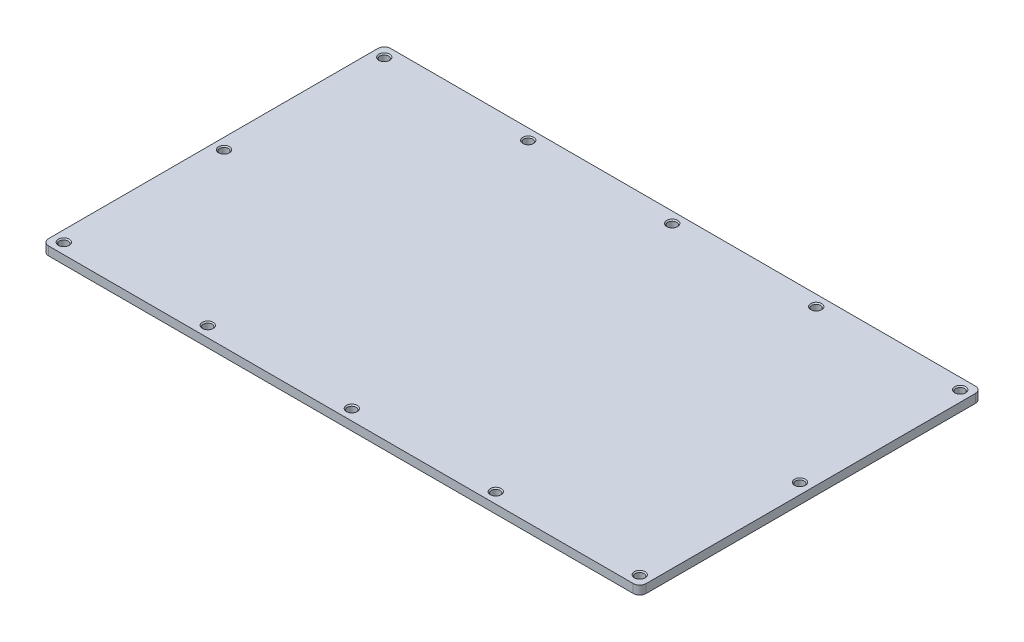
SolidWorks part; units mm, degrees
ref_plane "Front Plane" through (0, 0, 0) normal (0, 0, 1) x (1, 0, 0)
ref_plane "Top Plane" through (0, 0, 0) normal (0, 1, 0) x (1, 0, 0)
ref_plane "Right Plane" through (0, 0, 0) normal (1, 0, 0) x (0, 0, -1)
sketch "Sketch1" plane through (0, 0, 0) normal (0, 1, 0) x (1, 0, 0)
  line L0 (0, 0) -> (0, 158)
  line L1 (0, 158) -> (276, 158)
  line L2 (276, 158) -> (276, 0)
  line L3 (276, 0) -> (0, 0)
  dimension "D1" = 276
  dimension "D2" = 158
extrude "Boss-Extrude1" add sketch "Sketch1" along normal blind 4
sketch "Sketch2" plane through (0, 0, 0) normal (0, 1, 0) x (1, 0, 0)
  line L0 (5, 158) -> (5, 0) construction
  line L1 (276, 158) -> (0, 158) construction
  line L2 (0, 0) -> (276, 0) construction
  line L3 (0, 158) -> (0, 0) construction
  circle A0 centre (5, 79) radius 2
  dimension "D2" = 4
  dimension "D1" = 5
extrude "Cut-Extrude1" cut sketch "Sketch2" along normal blind 10
pattern_linear "LPattern1" count 2 spacing 74 along (0, 0, 1) count 2 spacing 74 along (0, 0, -1) of "Cut-Extrude1"
pattern_linear "LPattern2" count 5 spacing 66.5 along (1, 0, 0) of "LPattern1", "Cut-Extrude1"
fillet "Fillet1" radius 3 4 edges at (276, 2, 0) (276, 2, -158) (0, 2, -158) (0, 2, 0)
sketch "Sketch3" plane through (0, 0, 0) normal (0, 1, 0) x (1, 0, 0)
  line L0 (30.6341, 126.4888) -> (231.0215, 126.4888)
  line L1 (231.0215, 126.4888) -> (231.0215, 31.9459)
  line L2 (231.0215, 31.9459) -> (30.6341, 31.9459)
  line L3 (30.6341, 31.9459) -> (30.6341, 126.4888)
extrude "Boss-Extrude2" add sketch "Sketch3" along normal blind 4
chamfer "Chamfer1" distance 0.5 angle 45 12 edges at (271, 4, -81) (271, 4, -155) (204.5, 4, -155) (138, 4, -155) (271, 4, -7) (204.5, 4, -7) (138, 4, -7) (5, 4, -81) (5, 4, -155) (5, 4, -7) (71.5, 4, -7) (71.5, 4, -155)
sketch "Sketch4" plane through (0, 0, 0) normal (0, -1, 0) x (1, 0, 0)
  line L0 (10.1, -15.1) -> (10.1, -142.9)
  line L1 (15.1, -20.1) -> (15.1, -137.9)
  line L2 (15.1, -10.1) -> (260.9, -10.1)
  line L3 (265.9, -15.1) -> (265.9, -142.9)
  line L4 (260.9, -147.9) -> (15.1, -147.9)
  line L5 (255.9, -142.9) -> (20.1, -142.9)
  line L6 (260.9, -20.1) -> (260.9, -137.9)
  line L7 (20.1, -15.1) -> (255.9, -15.1)
  line L8 (15.1, -15.1) -> (15.1, -142.9) construction
  line L9 (260.9, -142.9) -> (15.1, -142.9) construction
  line L10 (260.9, -15.1) -> (260.9, -142.9) construction
  line L11 (15.1, -15.1) -> (260.9, -15.1) construction
  circle A0 centre (5, -79) radius 2 construction
  circle A1 centre (138, -5) radius 2 construction
  circle A2 centre (271, -79) radius 2 construction
  circle A3 centre (138, -153) radius 2 construction
  arc A4 (10.1, -142.9) -> (15.1, -147.9) centre (15.1, -142.9) ccw
  arc A5 (260.9, -147.9) -> (265.9, -142.9) centre (260.9, -142.9) ccw
  arc A6 (265.9, -15.1) -> (260.9, -10.1) centre (260.9, -15.1) ccw
  arc A7 (15.1, -10.1) -> (10.1, -15.1) centre (15.1, -15.1) ccw
  arc A12 (15.1, -137.9) -> (20.1, -142.9) centre (20.1, -137.9) ccw
  arc A13 (15.1, -142.9) -> (15.1, -142.9) centre (15.1, -142.9) ccw construction
  arc A14 (255.9, -142.9) -> (260.9, -137.9) centre (255.9, -137.9) ccw
  arc A15 (260.9, -142.9) -> (260.9, -142.9) centre (260.9, -142.9) ccw construction
  arc A16 (260.9, -20.1) -> (255.9, -15.1) centre (255.9, -20.1) ccw
  arc A17 (260.9, -15.1) -> (260.9, -15.1) centre (260.9, -15.1) ccw construction
  arc A18 (20.1, -15.1) -> (15.1, -20.1) centre (20.1, -20.1) ccw
  arc A19 (15.1, -15.1) -> (15.1, -15.1) centre (15.1, -15.1) ccw construction
  dimension "D1" = 5.1
  dimension "D5" = 5
  dimension "D7" = 5
  dimension "D2" = 5.1
  dimension "D3" = 5.1
  dimension "D4" = 5.1
  dimension "D6" = 5
extrude "Boss-Extrude3" add sketch "Sketch4" along normal blind 5 contours L2 A7 L0 A4 L4 A5 L3 A6 A18 L7 A16 L6 A14 L5 A12 L1 | L7 A18 L1 A12 L5 A14 L6 A16
sketch "Sketch5" plane through (0, 0, 0) normal (0, -1, 0) x (1, 0, 0)
  line L0 (15.1, -20.1) -> (255.9, -142.9) construction
  line L1 (260.9, -137.9) -> (20.1, -15.1) construction
  line L2 (255.9, -15.1) -> (15.1, -137.9) construction
  line L3 (20.1, -142.9) -> (260.9, -20.1) construction
  line L4 (40.9104, -142.9) -> (235.0896, -142.9)
  line L5 (237.3611, -133.4458) -> (140.2715, -83.9333)
  line L6 (135.7285, -83.9333) -> (38.6389, -133.4458)
  line L7 (22.3715, -134.1918) -> (121.8634, -83.4542)
  line L8 (121.8634, -74.5458) -> (22.3715, -23.8082)
  line L9 (15.1, -28.2625) -> (15.1, -129.7375)
  line L10 (38.6389, -24.5542) -> (135.7285, -74.0667)
  line L11 (140.2715, -74.0667) -> (237.3611, -24.5542)
  line L12 (235.0896, -15.1) -> (40.9104, -15.1)
  line L13 (253.6285, -134.1918) -> (154.1366, -83.4542)
  line L14 (154.1366, -74.5458) -> (253.6285, -23.8082)
  line L15 (260.9, -28.2625) -> (260.9, -129.7375)
  arc A0 (40.9104, -142.9) -> (38.6389, -133.4458) centre (40.9104, -137.9) cw
  arc A1 (235.0896, -142.9) -> (237.3611, -133.4458) centre (235.0896, -137.9) ccw
  arc A2 (140.2715, -83.9333) -> (135.7285, -83.9333) centre (138, -88.3876) ccw
  arc A3 (154.1366, -83.4542) -> (154.1366, -74.5458) centre (156.4082, -79) cw
  arc A4 (253.6285, -134.1918) -> (260.9, -129.7375) centre (255.9, -129.7375) ccw
  arc A5 (260.9, -28.2625) -> (253.6285, -23.8082) centre (255.9, -28.2625) ccw
  arc A6 (237.3611, -24.5542) -> (235.0896, -15.1) centre (235.0896, -20.1) ccw
  arc A7 (140.2715, -74.0667) -> (135.7285, -74.0667) centre (138, -69.6124) cw
  arc A8 (40.9104, -15.1) -> (38.6389, -24.5542) centre (40.9104, -20.1) ccw
  arc A9 (15.1, -28.2625) -> (22.3715, -23.8082) centre (20.1, -28.2625) cw
  arc A10 (121.8634, -83.4542) -> (121.8634, -74.5458) centre (119.5918, -79) ccw
  arc A11 (22.3715, -134.1918) -> (15.1, -129.7375) centre (20.1, -129.7375) cw
  point P25 (138, -82.7749)
  point P31 (145.4023, -79)
  point P43 (138, -75.2251)
  point P52 (130.5977, -79)
  dimension "D1" = 5
  dimension "D2" = 5
extrude "Cut-Extrude2" cut sketch "Sketch5" against normal blind 2
sketch "Sketch6" plane through (0, 0, 0) normal (0, -1, 0) x (1, 0, 0)
  line L0 (138, -15.1) -> (138, -147.9) construction
  line L1 (235.0896, -15.1) -> (40.9104, -15.1) construction
  line L2 (260.9, -147.9) -> (15.1, -147.9) construction
  line L3 (133, -15.1) -> (133, -64.5128)
  line L4 (133, -147.9) -> (143, -147.9)
  line L5 (143, -64.5128) -> (143, -15.1)
  line L6 (143, -15.1) -> (133, -15.1)
  line L7 (133, -15.1) -> (113, -15.1)
  line L8 (143, -15.1) -> (163, -15.1)
  line L9 (20.1, -15.1) -> (255.9, -15.1) construction
  line L10 (133, -15.1) -> (133, -35.1)
  line L11 (143, -15.1) -> (163, -15.1)
  line L12 (143, -15.1) -> (143, -35.1)
  line L13 (143, -142.9) -> (163, -142.9)
  line L14 (255.9, -142.9) -> (20.1, -142.9) construction
  line L15 (40.9104, -142.9) -> (235.0896, -142.9) construction
  line L16 (143, -142.9) -> (143, -122.9)
  line L17 (133, -142.9) -> (113, -142.9)
  line L18 (133, -142.9) -> (133, -122.9)
  line L19 (113, -62.4759) -> (125.7285, -68.967)
  line L20 (38.6389, -24.5542) -> (135.7285, -74.0667) construction
  line L21 (143, -64.5128) -> (143, -85.3248) construction
  line L22 (163, -62.4759) -> (150.2715, -68.967)
  line L23 (140.2715, -74.0667) -> (237.3611, -24.5542) construction
  line L24 (133, -64.5128) -> (133, -85.3248) construction
  line L25 (135.7285, -83.9333) -> (38.6389, -133.4458) construction
  line L26 (237.3611, -133.4458) -> (140.2715, -83.9333) construction
  line L27 (133, -93.4872) -> (133, -122.9)
  line L28 (143, -93.4872) -> (143, -122.9)
  line L29 (133, -122.9) -> (143, -122.9)
  line L30 (133, -142.9) -> (143, -142.9)
  line L31 (125.7285, -89.033) -> (113, -95.5241)
  line L32 (150.2715, -89.033) -> (163, -95.5241)
  line L33 (113, -95.5241) -> (113, -91.1094)
  line L34 (113, -91.1094) -> (128, -82.1747)
  line L35 (128, -82.1747) -> (122.4613, -72.01)
  line L36 (122.4613, -72.01) -> (110.6131, -64.5128)
  line L37 (110.6131, -64.5128) -> (113, -62.4759)
  line L38 (163, -62.4759) -> (164.2214, -63.9072)
  line L39 (164.2214, -63.9072) -> (150.2715, -73.758)
  line L40 (150.2715, -73.758) -> (149.7184, -83.6638)
  line L41 (149.7184, -83.6638) -> (165.5328, -91.7287)
  line L42 (165.5328, -91.7287) -> (163, -95.5241)
  arc A0 (113, -15.1) -> (133, -35.1) centre (113, -35.1) cw
  arc A1 (143, -35.1) -> (163, -15.1) centre (163, -35.1) cw
  arc A2 (113, -142.9) -> (133, -122.9) centre (113, -122.9) ccw
  arc A3 (143, -122.9) -> (163, -142.9) centre (163, -122.9) ccw
  arc A4 (133, -64.5128) -> (125.7285, -68.967) centre (128, -64.5128) cw
  arc A5 (143, -64.5128) -> (150.2715, -68.967) centre (148, -64.5128) ccw
  arc A6 (150.2715, -89.033) -> (143, -93.4872) centre (148, -93.4872) ccw
  arc A7 (133, -93.4872) -> (125.7285, -89.033) centre (128, -93.4872) ccw
  line M20 (237.3611, -24.5542) -> (140.2715, -74.0667)
  arc M21 (140.2715, -74.0667) -> (135.7285, -74.0667) centre (138, -69.6124) cw
  line M22 (135.7285, -74.0667) -> (38.6389, -24.5542)
  line M36 (38.6389, -133.4458) -> (135.7285, -83.9333)
  arc M37 (135.7285, -83.9333) -> (140.2715, -83.9333) centre (138, -88.3876) cw
  line M38 (140.2715, -83.9333) -> (237.3611, -133.4458)
  dimension "D12" = 5
  dimension "D13" = 5
  dimension "D14" = 5
  dimension "D1" = 5
  dimension "D2" = 5
  dimension "D3" = 20
  dimension "D4" = 20
  dimension "D5" = 20
  dimension "D6" = 20
  dimension "D7" = 20
  dimension "D8" = 20
  dimension "D9" = 20
  dimension "D10" = 20
  dimension "D11" = 20
extrude "Boss-Extrude4" add sketch "Sketch6" against normal blind 3 contours A2 L17 L18 | L18 L30 L16 L29 | A7 L27 L29 L28 A6 M38 M37 M36 | L42 L41 L40 L39 L38 L37 L36 L35 L34 L33 M20 M21 M22 M36 M37 M38 | A5 L5 L6 L3 A4 M22 M21 M20 | L7 A0 L3 | L5 A1 L8 | A3 L16 L13
chamfer "Chamfer2" distance 0.5 angle 45 8 edges at (265.9, -5, -79) (264.4355, -5, -11.5645) (264.4355, -5, -146.4355) (138, -5, -10.1) (138, -5, -147.9) (11.5645, -5, -11.5645) (11.5645, -5, -146.4355) (10.1, -5, -79)
chamfer "Chamfer4" distance 2 angle 45 36 edges at (199.0448, 2, -15.1) (239.9512, 2, -18.9319) (193.8163, 2, -46.7606) (145.3883, 2, -68.7764) (143, 2, -49.8064) (148.8579, 2, -20.9579) (82.1837, 2, -46.7606) (36.0488, 2, -18.9319) (76.9552, 2, -15.1) (127.1421, 2, -20.9579) (133, 2, -49.8064) (130.6117, 2, -68.7764) (72.1174, 2, -49.177) (124.5918, 2, -79) (72.1174, 2, -108.823) (17.4883, 2, -134.0012) (15.1, 2, -79) (17.4883, 2, -23.9988) (76.9552, 2, -142.9) (36.0488, 2, -139.0681) (82.1837, 2, -111.2394) (130.6117, 2, -89.2236) (133, 2, -108.1936) (127.1421, 2, -137.0421) (193.8163, 2, -111.2394) (239.9512, 2, -139.0681) (199.0448, 2, -142.9) (148.8579, 2, -137.0421) (143, 2, -108.1936) (145.3883, 2, -89.2236) (258.5117, 2, -23.9988) (203.8826, 2, -49.177) (260.9, 2, -79) (151.4082, 2, -79) (258.5117, 2, -134.0012) (203.8826, 2, -108.823)
